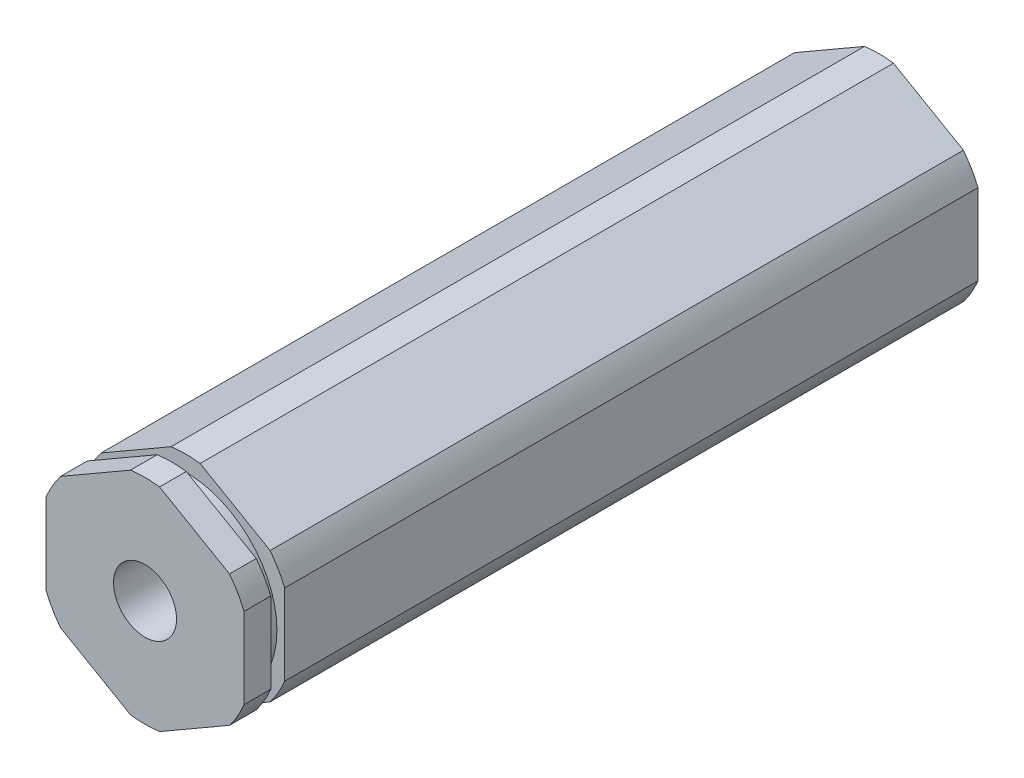
SolidWorks part; units mm, degrees
ref_plane "Front Plane" through (0, 0, 0) normal (0, 0, 1) x (1, 0, 0)
ref_plane "Top Plane" through (0, 0, 0) normal (0, 1, 0) x (1, 0, 0)
ref_plane "Right Plane" through (0, 0, 0) normal (1, 0, 0) x (0, 0, -1)
sketch "Sketch1" plane through (0, 0, 0) normal (0, 0, 1) x (1, 0, 0)
  line L1 (0, 7.3323) -> (-6.35, 3.6662)
  line L2 (-6.35, 3.6662) -> (-6.35, -3.6662)
  line L3 (-6.35, -3.6662) -> (0, -7.3323)
  line L4 (0, -7.3323) -> (6.35, -3.6662)
  line L5 (6.35, -3.6662) -> (6.35, 3.6662)
  line L6 (6.35, 3.6662) -> (0, 7.3323)
  circle A0 centre (0, 0) radius 6.35 construction
  circle A1 centre (0, 0) radius 6.858
  dimension "D1" = 12.7
  dimension "D2" = 13.716
extrude "Boss-Extrude1" add sketch "Sketch1" along normal mid plane 47.0662 contours L5 A1 L6 L1 L2 L3 L4 region at (0, 0, 0)
sketch "Sketch6" plane through (0, 0, 0) normal (0, 0, 1) x (1, 0, 0)
  line L0 (5.4183, 4.2041) -> (0.9317, 6.7944) construction
  circle A0 centre (0, 0) radius 6.35
hole_wizard "#10-32 Tapped Hole1" positions "3DSketch1" profile "Sketch2" tap size "#10-32" standard "ANSI Inch"
sketch3d "3DSketch1"
  line L0 (0, 0, 23.5331) -> (0, 0, -23.5331) construction
  line L1 (0, 0, 23.5331) -> (0, 0, -23.5331) construction
  point P0 (0, 0, 23.5331)
  point P4 (0, 0, -23.5331)
sketch "Sketch2" plane through (0, 0, 23.5331) normal (1, 0, 0) x (0, -1, 0)
  line L0 (0, 0) -> (0, 17.5608)
  line L1 (0, 17.5608) -> (2.0193, 16.3474)
  line L2 (2.0193, 16.3474) -> (2.0193, 0)
  line L5 (2.0193, 0) -> (0, 0)
  line L10 (0, 17.5608) -> (-2.0193, 16.3474) construction
  line L11 (0, -6.35) -> (0, 107.95) construction
  dimension "Tap Drill Dia." = 4.0386
  dimension "Tap Drill Depth" = 16.3474
  dimension "Drill Angle" = 118
cosmetic thread "Hole Thread1" parameters "D1"=13.97, "D2"=4.826
cosmetic thread "Hole Thread2" parameters "D1"=13.97, "D2"=4.826
sketch "Sketch5" plane through (0, 0, 0) normal (1, 0, 0) x (0, 0, -1)
  line L0 (23.5331, 6.858) -> (-23.5331, 6.858) construction
  line L1 (-21.8186, 6.858) -> (-20.9296, 6.858)
  line L2 (-21.8186, 6.858) -> (-21.8186, 5.8547)
  line L3 (-21.8186, 5.8547) -> (-20.9296, 5.8547)
  line L4 (-20.9296, 6.858) -> (-20.9296, 5.8547)
  line L5 (-165.0472, 0) -> (-158.8423, 0) construction
  dimension "D1" = 5.8547
  dimension "D2" = 0.889
  dimension "D3" = 1.7145
revolve "Cut-Revolve1" cut sketch "Sketch5" angle 360 about L5
